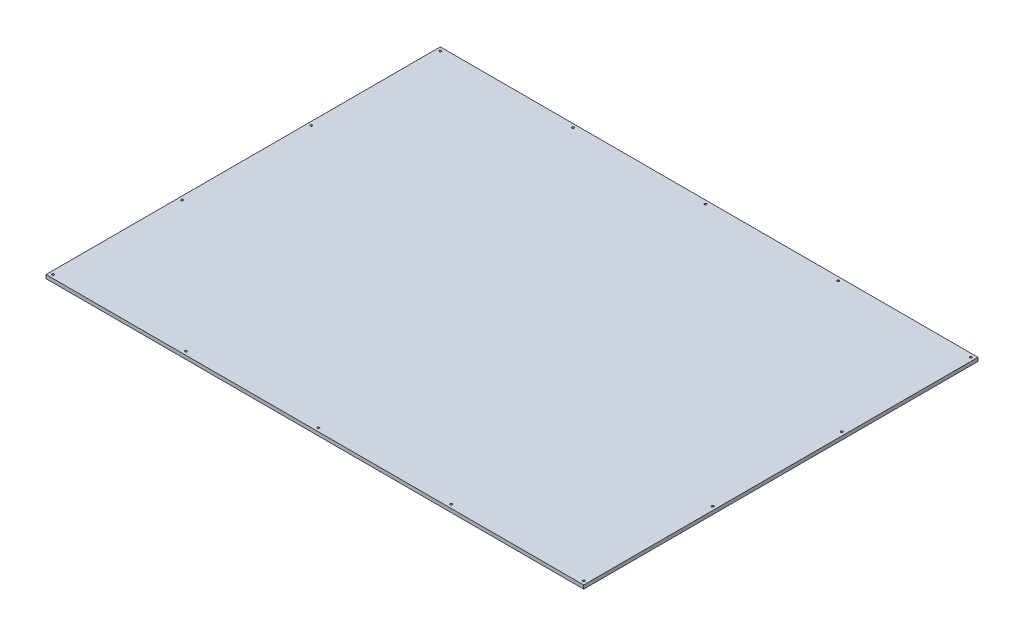
SolidWorks part; units mm, degrees
ref_plane "Front Plane" through (0, 0, 0) normal (0, 0, 1) x (1, 0, 0)
ref_plane "Top Plane" through (0, 0, 0) normal (0, 1, 0) x (1, 0, 0)
ref_plane "Right Plane" through (0, 0, 0) normal (1, 0, 0) x (0, 0, -1)
sketch "Sketch1" plane through (0, 0, 0) normal (0, 1, 0) x (1, 0, 0)
  line L0 (-375, 275) -> (375, 275)
  line L1 (-380, -280) -> (380, -280) construction
  line L2 (-380, -280) -> (-380, 280) construction
  line L3 (-380, 280) -> (380, 280) construction
  line L4 (380, -280) -> (380, 280) construction
  line L5 (-380, -280) -> (380, 280) construction
  line L6 (-380, 280) -> (380, -280) construction
  line L7 (375, -275) -> (375, 275)
  line L8 (-375, -275) -> (375, -275)
  line L9 (-375, -275) -> (-375, 275)
  point P0 (0, 0)
  dimension "D1" = 760
  dimension "D2" = 560
  dimension "D3" = 5
extrude "Boss-Extrude1" add sketch "Sketch1" along normal blind 5
sketch "Sketch2" plane through (0, 5, 0) normal (0, 1, 0) x (1, 0, 0)
  line L0 (375, 275) -> (-375, 275) construction
  line L5 (-370, 0) -> (370, 0) construction
  line L7 (-370, -270) -> (370, -270) construction
  line L8 (-370, -270) -> (-370, 270) construction
  line L9 (-370, 270) -> (370, 270) construction
  line L10 (370, -270) -> (370, 270) construction
  line L11 (-370, -270) -> (370, 270) construction
  line L12 (-370, 270) -> (370, -270) construction
  line L13 (375, -275) -> (375, 275) construction
  line L14 (0, 270) -> (0, -270) construction
  circle A1 centre (-370, 270) radius 1.5
  circle A2 centre (-185, 270) radius 1.5
  circle A3 centre (0, 270) radius 1.5
  circle A4 centre (185, 270) radius 1.5
  circle A5 centre (370, 270) radius 1.5
  circle A6 centre (-370, 90) radius 1.5
  circle A7 centre (-370, -90) radius 1.5
  circle A8 centre (-370, -270) radius 1.5
  circle A9 centre (370, -270) radius 1.5
  circle A10 centre (185, -270) radius 1.5
  circle A11 centre (0, -270) radius 1.5
  circle A12 centre (-185, -270) radius 1.5
  circle A13 centre (-370, -270) radius 1.5
  circle A14 centre (370, -90) radius 1.5
  circle A15 centre (370, 90) radius 1.5
  point P0 (0, 0)
  point P6 (0, 0)
  dimension "D1" = 3
  dimension "D2" = 5
  dimension "D3" = 5
  dimension "D4" = 5
  dimension "D5" = 4
extrude "Cut-Extrude1" cut sketch "Sketch2" against normal through all contours A1 | A2 | A3 | A4 | A5 | A15 | A14 | A9 | A10 | A11 | A12 | A8 | A7 | A6 region at (-370, 5, -270) region at (-185, 5, -270) region at (0, 5, -270) region at (185, 5, -270) region at (370, 5, -270) region at (-370, 5, 270) region at (370, 5, 270) region at (185, 5, 270) region at (0, 5, 270) region at (-185, 5, 270) region at (370, 5, 90) region at (370, 5, -90)
equation "\"Crossbar_Width\"= 80mm"
equation "\"Vertical_Offset\"= \"Crossbar_Width\" / 2"
equation "\"Toolhead_Width\"= 100mm"
equation "\"Mechanical_Buffer\"= 30mm"
equation "\"Z_Interstitial\"= 100mm"
equation "\"Z_Interstitial_Sketch\"= \"Z_Interstitial\" + 1in"
